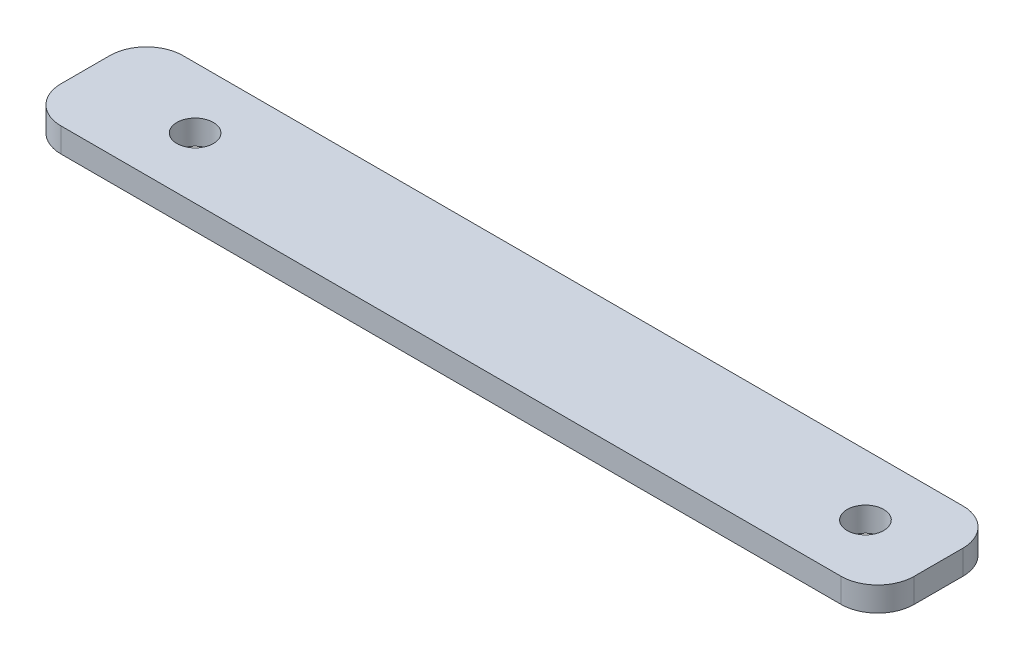
SolidWorks part; units mm, degrees
ref_plane "Front Plane" through (0, 0, 0) normal (0, 0, 1) x (1, 0, 0)
ref_plane "Top Plane" through (0, 0, 0) normal (0, 1, 0) x (1, 0, 0)
ref_plane "Right Plane" through (0, 0, 0) normal (1, 0, 0) x (0, 0, -1)
sketch "Sketch1" plane through (0, 0, 0) normal (0, 1, 0) x (1, 0, 0)
  line L1 (-35, 5) -> (35, 5)
  line L2 (-35, 5) -> (-35, -5)
  line L3 (-35, -5) -> (35, -5)
  line L4 (35, 5) -> (35, -5)
  line L5 (-35, 5) -> (35, -5) construction
  line L6 (-35, -5) -> (35, 5) construction
  point P0 (0, 0)
  dimension "D1" = 10
  dimension "D2" = 70
extrude "Boss-Extrude1" add sketch "Sketch1" along normal blind 2
sketch "Sketch2" plane through (0, 2, 0) normal (0, 1, 0) x (1, 0, 0)
  point P10 (26.3156, 0)
fillet "Fillet1" radius 3 4 edges at (35, 1, 5) (35, 1, -5) (-35, 1, 5) (-35, 1, -5)
hole_wizard "Ø3.0mm Dowel Hole1" positions "Sketch5" profile "Sketch6" hole size "Ø3.0" standard "ISO" end condition through all
sketch "Sketch5" plane through (0, 0, 0) normal (0, -1, 0) x (-1, 0, 0)
  line L1 (-35, -2) -> (-35, 2) construction
  line L3 (35, 0) -> (-35, 0) construction
  line L4 (35, 2) -> (35, -2) construction
  point P0 (-29, 0)
  point P2 (26, 0)
  dimension "D2" = 6
  dimension "=globalength1" = 55
sketch "Sketch6" plane through (29, 0, 0) normal (1, 0, 0) x (0, 0, -1)
  line L0 (0, 0) -> (0, 2)
  line L1 (0, 2) -> (1.5, 2)
  line L2 (1.5, 2) -> (1.5, 0)
  line L5 (1.5, 0) -> (0, 0)
  line L11 (0, -6.35) -> (0, 107.95) construction
  dimension "Thru Hole Dia." = 3
  dimension "Thru Hole Depth" = 2
equation "\"globalength1\"=55"
